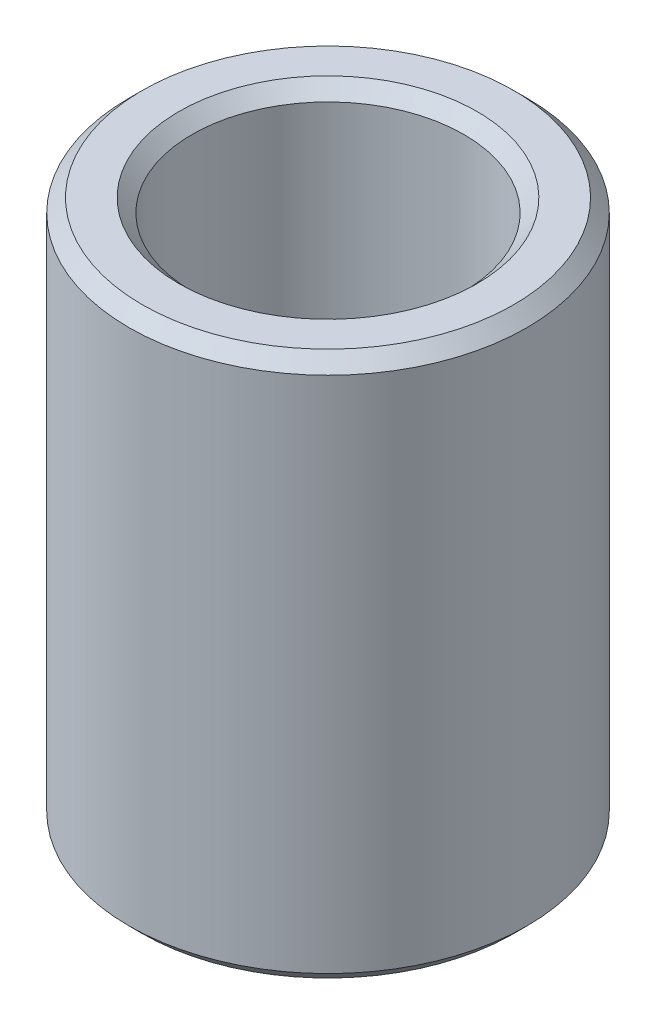
SolidWorks part; units mm, degrees
ref_plane "Front Plane" through (0, 0, 0) normal (0, 0, 1) x (1, 0, 0)
ref_plane "Top Plane" through (0, 0, 0) normal (0, 1, 0) x (1, 0, 0)
ref_plane "Right Plane" through (0, 0, 0) normal (1, 0, 0) x (0, 0, -1)
sketch "Sketch1" plane through (0, 0, 0) normal (0, 1, 0) x (1, 0, 0)
  circle A0 centre (0, 0) radius 57.5
  dimension "SLEEVE_OD" = 115
extrude "Boss-Extrude1" add sketch "Sketch1" along normal blind 157.4543
sketch "Sketch2" plane through (0, 0, 0) normal (0, 1, 0) x (1, 0, 0)
  circle A0 centre (0, 0) radius 39.2808
  dimension "BORE_D" = 78.5615
extrude "Cut-Extrude1" cut sketch "Sketch2" along normal through all
chamfer "Chamfer1" distance 3.8284 angle 45 4 edges at (0, 157.4543, 39.2808) (0, 0, 39.2808) (0, 0, 57.5) (0, 157.4543, 57.5)
